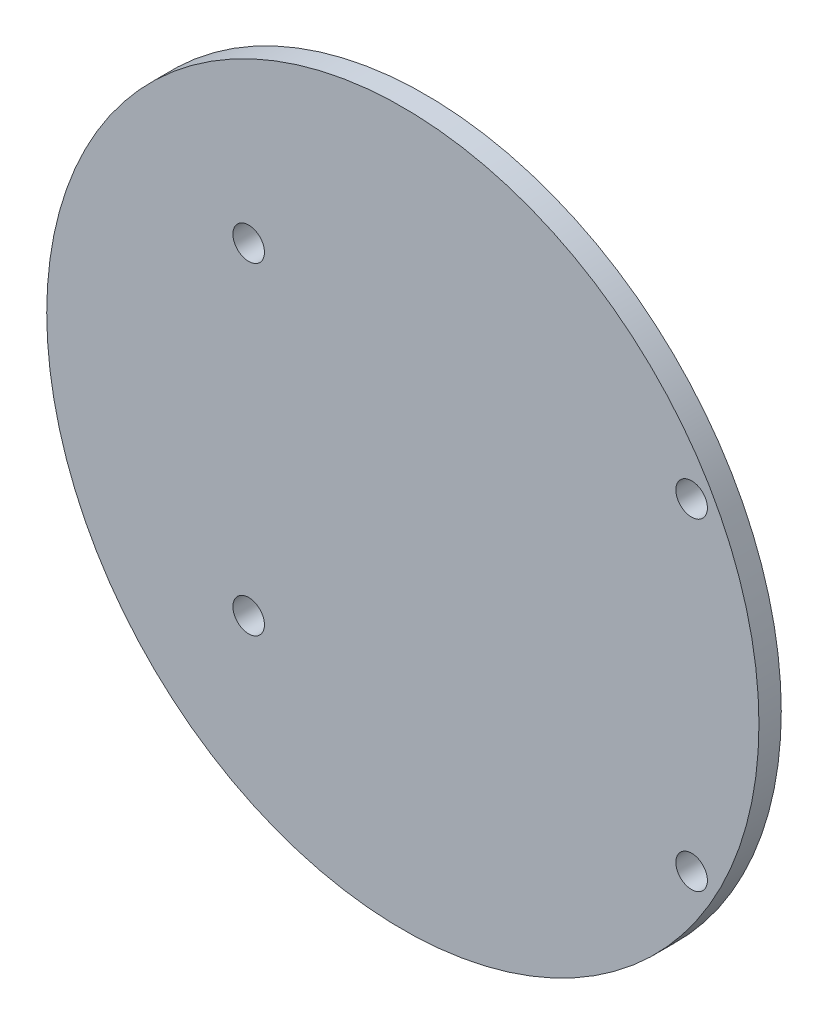
SolidWorks part; units mm, degrees
ref_plane "Front Plane" through (0, 0, 0) normal (0, 0, 1) x (1, 0, 0)
ref_plane "Top Plane" through (0, 0, 0) normal (0, 1, 0) x (1, 0, 0)
ref_plane "Right Plane" through (0, 0, 0) normal (1, 0, 0) x (0, 0, -1)
sketch "Sketch1" plane through (0, 0, 0) normal (0, 0, 1) x (1, 0, 0)
  circle A0 centre (27.94, 27.94) radius 25.527
  dimension "D1" = 51.054
extrude "BOARD" add sketch "Sketch1" along normal blind 1.6 separate body
sketch "Sketch2" plane through (0, 0, 0) normal (0, 0, 1) x (1, 0, 0)
  circle A0 centre (48.64, 39.5) radius 1.13
  circle A1 centre (48.64, 16.38) radius 1.13
  circle A2 centre (16.89, 39.5) radius 1.13
  circle A3 centre (16.89, 16.38) radius 1.13
extrude "NON-PLATED HOLES" cut sketch "Sketch2" along normal through all
ref_plane "Plane1" through (0, 0, 2.4) normal (0, 0, 1) x (1, 0, 0)
sketch "Sketch3" plane through (0, 0, 0) normal (0, 0, -1) x (-1, 0, 0)
  line L0 (-48.64, 16.38) -> (-48.64, 7.109) construction
  line L1 (-48.64, 7.109) -> (-42.6946, 7.109) construction
  circle A0 centre (-27.94, 27.94) radius 25.527 construction
  dimension "D1" = 9.271
